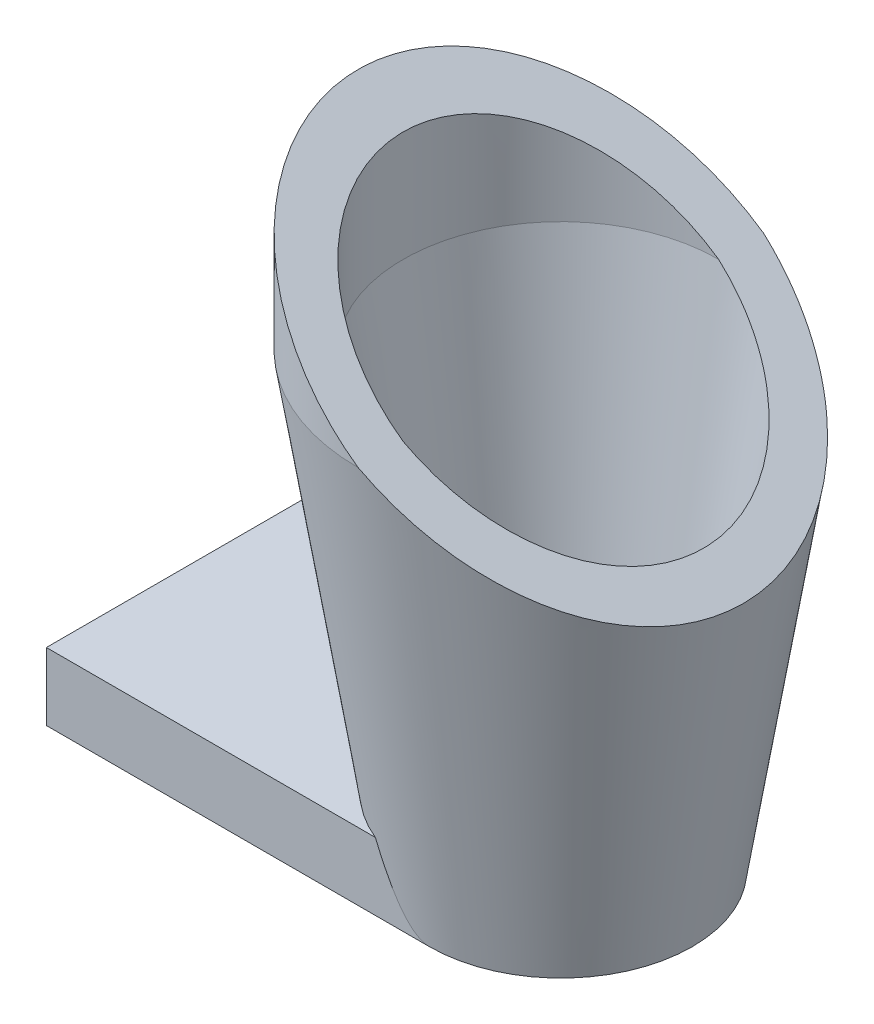
SolidWorks part; units mm, degrees
note: The reader was unsure of these and kept them because the rebuilt part matched: shared geometry of "Sketch1<4>", "Sketch1<5>".
ref_plane "Płaszczyzna przednia" through (0, 0, 0) normal (0, 0, 1) x (1, 0, 0)
ref_plane "Płaszczyzna górna" through (0, 0, 0) normal (0, 1, 0) x (1, 0, 0)
ref_plane "Płaszczyzna prawa" through (0, 0, 0) normal (1, 0, 0) x (0, 0, -1)
sketch "Sketch1" plane through (0, 0, 0) normal (0, 1, 0) x (1, 0, 0)
  line L0 (-23.1146, 0) -> (1132.6173, 0) construction
  line L1 (0, -23.1146) -> (0, 1132.6173) construction
  line L4 (0, 9) -> (0, -9)
  circle A0 centre (0, 0) radius 9
  circle A1 centre (0, 0) radius 7
  dimension "D1" = 18
  dimension "D2" = 14
extrude "Boss-Extrude1" add sketch "Sketch1" against normal blind 20 draft 9 and the other way blind 30 contours A0
ref_plane "Plane1" through (0, 0, 0) normal (0.5736, 0.8192, 0) x (0, 0, -1)
other "SurfaceCut1"
sketch "Sketch2" plane through (0, -20, 0) normal (0, -1, 0) x (1, 0, 0)
  line L0 (0, -9) -> (0, 9) construction
  circle A0 centre (0, 0) radius 4
  dimension "D1" = 8
loft "Cut-Loft1" cut profiles "Sketch2" section "Sketch1<4>" section "Sketch2"
sketch "Sketch1<4>" plane through (0, 0, 0) normal (0, 1, 0) x (1, 0, 0) same geometry as "Sketch1"
extrude "Cut-Extrude1" cut sketch "Sketch1<5>" along normal blind 5 contours A1
sketch "Sketch1<5>" plane through (0, 0, 0) normal (0, 1, 0) x (1, 0, 0) same geometry as "Sketch1"
sketch "Sketch3" plane through (0, -20, 0) normal (0, -1, 0) x (1, 0, 0)
  line L0 (0, -9) -> (0, 9) construction
  line L1 (0, 5.8323) -> (-17, 5.8323)
  line L2 (0, 5.8323) -> (0, -5.8323)
  line L3 (0, -5.8323) -> (-17, -5.8323)
  line L4 (-17, 5.8323) -> (-17, -5.8323)
  circle A0 centre (0, 0) radius 5.8323 construction
  circle A1 centre (0, 0) radius 5.8323
  circle M2 centre (0, 0) radius 5.8323
  dimension "D1" = 17
extrude "Boss-Extrude3" add sketch "Sketch3" against normal blind 3 contours L1 L4 L3 M2
equation "\"outerdiameter\"= 30"
equation "\"wallthick\"= 2"
equation "\"angle\"= 35"
equation "\"innerdiam\"= 14"
equation "\"D2@Sketch1\"=\"innerdiam\""
